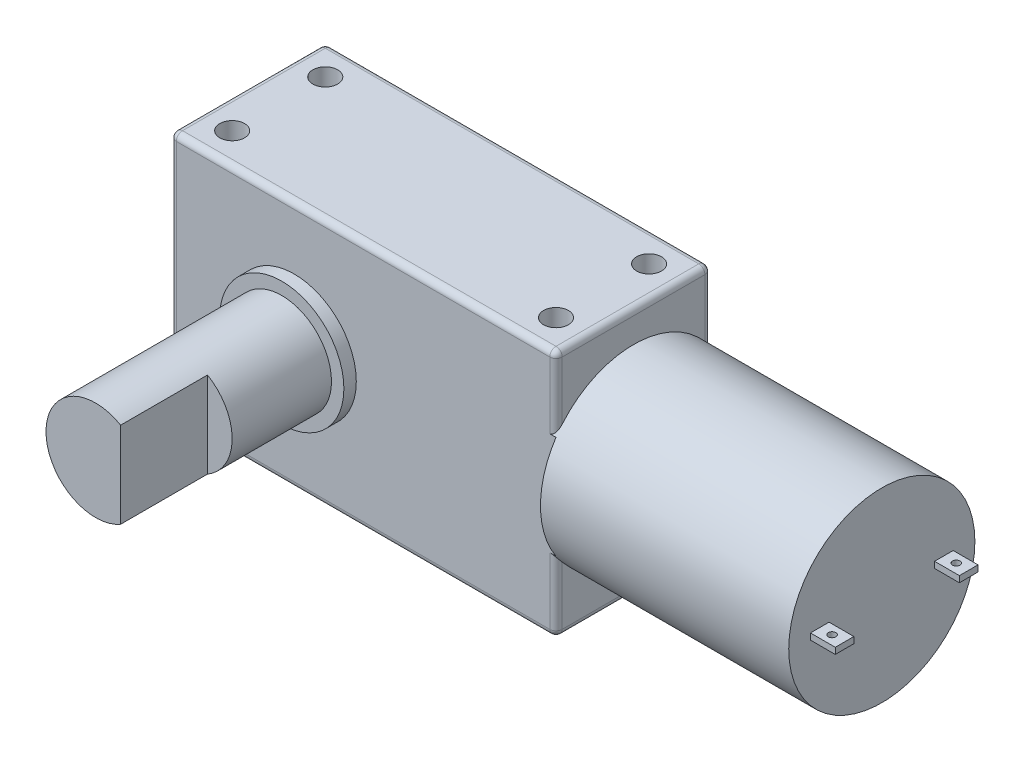
SolidWorks part; units mm, degrees
ref_plane "前视基准面" through (0, 0, 0) normal (0, 0, 1) x (1, 0, 0)
ref_plane "上视基准面" through (0, 0, 0) normal (0, 1, 0) x (1, 0, 0)
ref_plane "右视基准面" through (0, 0, 0) normal (1, 0, 0) x (0, 0, -1)
sketch "草图1" plane through (0, 0, 0) normal (0, 0, 1) x (1, 0, 0)
  line L1 (-25, 15) -> (25, 15)
  line L2 (-25, 15) -> (-25, -15)
  line L3 (-25, -15) -> (25, -15)
  line L4 (25, 15) -> (25, -15)
  line L5 (-25, 15) -> (25, -15) construction
  line L6 (-25, -15) -> (25, 15) construction
  point P0 (0, 0)
  dimension "D1" = 30
  dimension "D2" = 50
extrude "凸台-拉伸1" add sketch "草图1" along normal blind 25
sketch "草图2" plane through (0, 0, 25) normal (0, 0, 1) x (1, 0, 0)
  line L0 (-25, 15) -> (-25, 0)
  line L1 (-25, 15) -> (-25, -15) construction
  circle A0 centre (-15, 0) radius 2
  circle A1 centre (-15, 0) radius 5
  circle A2 centre (-15, 0) radius 1
  dimension "D1" = 15
  dimension "D2" = 10
extrude "凸台-拉伸2" add sketch "草图2" along normal blind 1 contours A1
sketch "草图3" plane through (0, 0, 26) normal (0, 0, 1) x (1, 0, 0)
  circle A0 centre (-15, 0) radius 4
extrude "凸台-拉伸3" add sketch "草图3" along normal blind 15 contours A0
sketch "草图6" plane through (0, 0, 25) normal (0, 0, 1) x (1, 0, 0)
  line L1 (-25, 10) -> (6.0886, 10)
  line L2 (-25, 10) -> (-25, -10)
  line L3 (-25, -10) -> (6.0886, -10)
  line L5 (-25, 10) -> (6.0886, -2.4354) construction
  line L6 (-25, -10) -> (6.0886, 2.4354) construction
  line L7 (6.0886, 10) -> (6.0886, -10)
  line L11 (-95.8005, 56.7098) -> (29.8501, 56.7098)
  line L12 (-95.8005, 56.7098) -> (-95.8005, -20.2323)
  line L13 (-95.8005, -20.2323) -> (29.8501, -20.2323)
  line L14 (29.8501, 56.7098) -> (29.8501, -20.2323)
  line L15 (-95.8005, 56.7098) -> (29.8501, -20.2323) construction
  line L16 (-95.8005, -20.2323) -> (29.8501, 56.7098) construction
  point P0 (0, 0)
  point P1 (-32.9752, 18.2387)
  dimension "D1" = 20
extrude "切除-拉伸1" cut sketch "草图6" against normal through all
sketch "草图7" plane through (6.0886, 0, 0) normal (1, 0, 0) x (0, 0, -1)
  line L0 (0, 10) -> (-25, 10) construction
  line L1 (-12.5, 10) -> (0, 10)
  line L2 (-12.5, 10) -> (-12.5, -10)
  line L3 (-12.5, -10) -> (0, -10)
  line L4 (0, 10) -> (0, -10)
extrude "切除-拉伸2" cut sketch "草图7" against normal through all
sketch "草图8" plane through (6.0886, 0, 0) normal (1, 0, 0) x (0, 0, -1)
  circle A0 centre (-18.75, 0) radius 7.5
extrude "凸台-拉伸5" add sketch "草图8" along normal blind 20
sketch "草图9" plane through (26.0886, 0, 0) normal (1, 0, 0) x (0, 0, -1)
  line L3 (-24.5, 0.25) -> (-23, 0.25)
  line L4 (-24.5, 0.25) -> (-24.5, -0.25)
  line L5 (-24.5, -0.25) -> (-23, -0.25)
  line L6 (-23, 0.25) -> (-23, -0.25)
  line L7 (-24.5, 0.25) -> (-23, -0.25) construction
  line L8 (-24.5, -0.25) -> (-23, 0.25) construction
  line L9 (-14.5, 0.25) -> (-13, 0.25)
  line L10 (-14.5, 0.25) -> (-14.5, -0.25)
  line L11 (-14.5, -0.25) -> (-13, -0.25)
  line L12 (-13, 0.25) -> (-13, -0.25)
  line L13 (-13.75, 0) -> (-13, -0.25) construction
  line L14 (-14.5, -0.25) -> (-13, 0.25) construction
  dimension "D3" = 1.5
  dimension "D4" = 0.5
  dimension "D5" = 0.5
  dimension "D6" = 1.5
extrude "凸台-拉伸6" add sketch "草图9" along normal blind 2
sketch "草图10" plane through (0, -0.25, 0) normal (0, -1, 0) x (1, 0, 0)
  circle A0 centre (27.0886, 23.75) radius 0.3
  circle A1 centre (27.0886, 13.75) radius 0.3
extrude "切除-拉伸3" cut sketch "草图10" against normal blind 2
fillet "圆角1" radius 0.5 14 edges at (-25, -10, 18.75) (-9.4557, -10, 25) (-9.4557, -10, 12.5) (6.0886, -10, 18.75) (6.0886, -7.0729, 12.5) (6.0886, -7.0729, 25) (6.0886, 7.0729, 12.5) (6.0886, 7.0729, 25) (6.0886, 10, 18.75) (-25, 0, 12.5) (-9.4557, 10, 12.5) (-25, 10, 18.75) (-25, 0, 25) (-9.4557, 10, 25)
sketch "草图11" plane through (0, 0, 41) normal (0, 0, 1) x (1, 0, 0)
  line L0 (-12.9892, 3.4578) -> (-12.9892, -3.4578)
  arc A2 (-12.9892, -3.4578) -> (-12.9892, 3.4578) centre (-15, 0) ccw
extrude "切除-拉伸4" cut sketch "草图11" against normal blind 7
sketch "草图12" plane through (0, -10, 0) normal (0, -1, 0) x (1, 0, 0)
  circle A0 centre (-22.5, 22.5) radius 1
  circle A1 centre (3.5886, 22.5) radius 1
  circle A2 centre (-22.5, 15) radius 1
  circle A3 centre (3.5886, 15) radius 1
extrude "切除-拉伸5" cut sketch "草图12" against normal through all
